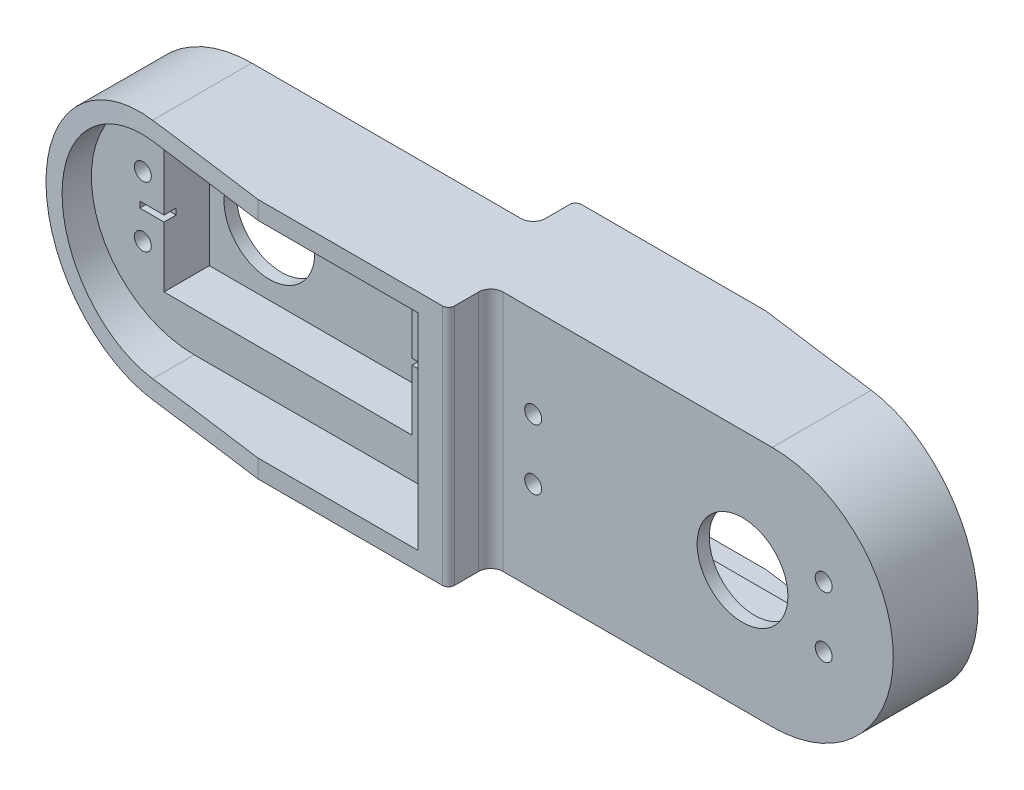
SolidWorks part; units mm, degrees
ref_plane "Front Plane" through (0, 0, 0) normal (0, 0, 1) x (1, 0, 0)
ref_plane "Top Plane" through (0, 0, 0) normal (0, 1, 0) x (1, 0, 0)
ref_plane "Right Plane" through (0, 0, 0) normal (1, 0, 0) x (0, 0, -1)
sketch "Sketch1" plane through (0, 0, 0) normal (0, 0, 1) x (1, 0, 0)
  line L0 (0, -20) -> (0, 20) construction
  line L1 (-69, -20) -> (69, -20)
  line L2 (-69, -20) -> (-69, 20)
  line L3 (-69, 20) -> (69, 20)
  line L4 (69, -20) -> (69, 20)
  line L5 (-69, -20) -> (69, 20) construction
  line L6 (-69, 20) -> (69, -20) construction
  line L7 (54, 10.5) -> (13, -10.5) construction
  line L8 (-54, -10.5) -> (-13, -10.5)
  line L9 (-54, -10.5) -> (-54, 10.5)
  line L10 (-54, 10.5) -> (-13, 10.5)
  line L11 (-13, -10.5) -> (-13, 10.5)
  line L12 (-54, -10.5) -> (-13, 10.5) construction
  line L13 (-54, 10.5) -> (-13, -10.5) construction
  line L14 (54, -10.5) -> (13, 10.5) construction
  line L15 (13, -10.5) -> (13, 10.5)
  line L16 (54, 10.5) -> (13, 10.5)
  line L17 (54, -10.5) -> (54, 10.5)
  line L18 (54, -10.5) -> (13, -10.5)
  point P0 (0, 0)
  point P6 (-33.5, 0)
  point P9 (0, 0)
  point P19 (33.5, 0)
  dimension "D1" = 138
  dimension "D2" = 40
  dimension "D3" = 15
  dimension "D4" = 41
  dimension "D5" = 21
extrude "Boss-Extrude1" add sketch "Sketch1" along normal blind 12
fillet "Fillet1" 2 edges at (-69, 20, 6) (-69, -20, 6) type full round first side face at (0, 20, 6) second side face at (0, -20, 6) middle face at (-69, 0, 6)
fillet "Fillet2" 2 edges at (69, 20, 6) (69, -20, 6) type full round first side face at (10, 20, 6) second side face at (10, -20, 6) middle face at (69, 0, 6)
sketch "Sketch3" plane through (0, 0, 12) normal (0, 0, 1) x (1, 0, 0)
  line L0 (49, 20) -> (-49, 20) construction
  line L1 (-2.5, -20) -> (2.5, -20)
  line L2 (-2.5, -17) -> (-2.5, 17)
  line L3 (-2.5, 20) -> (2.5, 20)
  line L4 (2.5, -20) -> (2.5, 20)
  line L5 (0, 0) -> (2.5, 20) construction
  line L6 (0, 0) -> (2.5, -20) construction
  line L7 (-49, 17) -> (-2.5, 17)
  line L8 (-49, -17) -> (-2.5, -17)
  line L9 (-2.5, 20) -> (-49, 20)
  line L10 (-49, -20) -> (2.5, -20)
  arc A1 (-49, 20) -> (-49, -20) centre (-49, 0) ccw
  arc A2 (-49, 17) -> (-49, -17) centre (-49, 0) ccw
  arc A3 (-49, 17) -> (-49, -17) centre (-49, 0) ccw
  point P0 (0, 0)
  line M9 (-49, -20) -> (49, -20)
  line M11 (49, 20) -> (-49, 20)
  arc M12 (-49, 20) -> (-49, -20) centre (-49, 0) ccw
  dimension "D2" = 5
  dimension "D1" = 3
extrude "Boss-Extrude3" add sketch "Sketch3" along normal blind 7 contours L4 A3 L7 L2 L8 M9 M11 M12 region at (-25.75, -19.1807, 12)
sketch "Sketch5" plane through (0, 0, 0) normal (0, 0, -1) x (-1, 0, 0)
  line L0 (-2.5, -20) -> (2.5, -20)
  line L1 (-2.5, -17) -> (-2.5, 17)
  line L2 (-2.5, 20) -> (2.5, 20)
  line L3 (2.5, -20) -> (2.5, 20)
  line L4 (0, 0) -> (2.5, 20) construction
  line L5 (0, 0) -> (2.5, -20) construction
  line L6 (-49, 17) -> (-2.5, 17)
  line L7 (-49, -17) -> (-2.5, -17)
  line L8 (-2.5, 20) -> (-49, 20)
  line L9 (-49, -20) -> (2.5, -20)
  line L10 (-69, 0) -> (-40.6504, 0) construction
  line L11 (-49, 20) -> (-49, -20) construction
  line L12 (13, -10.5) -> (13, 10.5) construction
  line L13 (49, -20) -> (-49, -20) construction
  arc A0 (-49, 20) -> (-49, -20) centre (-49, 0) ccw
  arc A1 (-49, 17) -> (-49, -17) centre (-49, 0) ccw
  arc A2 (-49, 20) -> (-49, -20) centre (-49, 0) ccw construction
  point P0 (37.3856, -38.3424)
  line M4 (49, 20) -> (-49, 20)
  arc M5 (-49, 20) -> (-49, -20) centre (-49, 0) ccw
  line M6 (-49, -20) -> (49, -20)
  dimension "D2" = 10.5
  dimension "D5" = 17
  dimension "D6" = 24.3856
  dimension "D7" = 18.3424
  dimension "D1" = 5
extrude "Boss-Extrude4" add sketch "Sketch5" along normal blind 7 contours L3 A1 L6 L1 L7 M6 M4 M5 region at (25.75, -19.1807, 0)
sketch "Sketch6" plane through (0, 0, 0) normal (0, 1, 0) x (1, 0, 0)
  line L0 (-69, -19) -> (-29, -19)
  line L1 (-69, -19) -> (-69, -14)
  line L2 (-69, 0) -> (-69, -19) construction
  line L3 (69, 7) -> (29, 7)
  line L4 (-2.5, 7) -> (49, 7) construction
  line L5 (69, 7) -> (69, 2)
  line L6 (69, -12) -> (69, 7) construction
  spline S0 degree 2 poles (-69, -14) (-48.9668, -16.2376) (-29, -19) knots 0 0 0 1 1 1
  spline S1 degree 2 poles (69, 2) (48.9668, 4.2376) (29, 7) knots 0 0 0 1 1 1
  dimension "D1" = 40
  dimension "D2" = 5
  dimension "D3" = 40
  dimension "D4" = 5
  dimension "D5" = 25
  dimension "D6" = 25
  dimension "D7" = 2
  dimension "D8" = 2
extrude "Cut-Extrude1" cut sketch "Sketch6" against normal through all both and the other way through all
sketch "Sketch8" plane through (0, 0, 12) normal (0, 0, 1) x (1, 0, 0)
  line L0 (-49, -17) -> (-2.5, -17) construction
  line L1 (-2.5, -17) -> (-2.5, 17) construction
  line L2 (-29, 17) -> (-2.5, 17) construction
  line L3 (-49, 17) -> (-29, 17) construction
  line L4 (-49, -17) -> (-2.5, -17)
  line L5 (-2.5, -17) -> (-2.5, 17)
  line L6 (-29, 17) -> (-2.5, 17)
  line L7 (-49, 17) -> (-29, 17)
  arc A0 (-49, 17) -> (-49, -17) centre (-49, 0) ccw construction
  arc A1 (-49, 17) -> (-49, -17) centre (-49, 0) ccw
extrude "Cut-Extrude2" cut sketch "Sketch8" against normal blind 2.5
sketch "Sketch9" plane through (0, 0, 0) normal (0, 0, -1) x (-1, 0, 0)
  line L0 (-49, -17) -> (-2.5, -17) construction
  line L1 (-2.5, -17) -> (-2.5, 17) construction
  line L2 (-49, 17) -> (-2.5, 17) construction
  line L3 (-49, 17) -> (-29, 17) construction
  line L4 (-49, -17) -> (-2.5, -17)
  line L5 (-2.5, -17) -> (-2.5, 17)
  line L6 (-49, 17) -> (-2.5, 17)
  line L7 (-49, 17) -> (-29, 17)
  arc A0 (-49, 17) -> (-49, -17) centre (-49, 0) ccw construction
  arc A1 (-49, 17) -> (-49, -17) centre (-49, 0) ccw
  line M1 (-13, -10.5) -> (-54, -10.5)
  line M2 (-54, -10.5) -> (-54, 10.5)
  line M3 (-54, 10.5) -> (-13, 10.5)
  line M4 (-13, 10.5) -> (-13, -10.5)
  line M5 (-2.5, 17) -> (-49, 17)
  arc M6 (-49, 17) -> (-49, -17) centre (-49, 0) ccw
  line M7 (-49, -17) -> (-2.5, -17)
  line M8 (-2.5, -17) -> (-2.5, 17)
extrude "Cut-Extrude3" cut sketch "Sketch9" against normal blind 2.5 contours L6 M8 M5 M6 M7 M4 M1 M2 M3 region at (65.2797, 0, 0)
sketch "Sketch10" plane through (0, 0, 12) normal (0, 0, 1) x (1, 0, 0)
  line L0 (54, -10.5) -> (54, 10.5) construction
  line L1 (13, -10.5) -> (54, -10.5) construction
  line L2 (13, 10.5) -> (13, -10.5) construction
  line L3 (54, 10.5) -> (13, 10.5) construction
  line L4 (54, -10.5) -> (54, 10.5)
  line L5 (13, -10.5) -> (54, -10.5)
  line L6 (13, 10.5) -> (13, -10.5)
  line L7 (54, 10.5) -> (13, 10.5)
  circle A0 centre (44.09, 0) radius 7.5
  point P7 (54, 0)
  dimension "D1" = 15
  dimension "D2" = 9.91
extrude "Boss-Extrude5" add sketch "Sketch10" against normal blind 2
sketch "Sketch11" plane through (0, 0, 0) normal (0, 0, -1) x (-1, 0, 0)
  line L0 (54, -10.5) -> (13, -10.5) construction
  line L1 (13, -10.5) -> (13, 10.5) construction
  line L2 (13, 10.5) -> (54, 10.5) construction
  line L3 (54, 10.5) -> (54, -10.5) construction
  line L4 (54, -10.5) -> (13, -10.5)
  line L5 (13, -10.5) -> (13, 10.5)
  line L6 (13, 10.5) -> (54, 10.5)
  line L7 (54, 10.5) -> (54, -10.5)
  circle A0 centre (44.09, 0) radius 7.5
  dimension "D1" = 15
  dimension "D2" = 9.91
extrude "Boss-Extrude6" add sketch "Sketch11" against normal blind 2
sketch "Sketch12" plane through (0, 0, 9.5) normal (0, 0, 1) x (1, 0, 0)
  line L0 (-66, 0) -> (-2.5, 0) construction
  line L1 (-2.5, -17) -> (-2.5, 17) construction
  line L2 (-54, 0.5) -> (-58, 0.5)
  line L3 (-54, -10.5) -> (-54, 10.5) construction
  line L4 (-58, 0.5) -> (-58, -0.5)
  line L5 (-58, -0.5) -> (-54, -0.5)
  line L6 (-33.5, 10.5) -> (-33.5, -10.5) construction
  line L7 (-54, 10.5) -> (-13, 10.5) construction
  line L8 (-13, -10.5) -> (-54, -10.5) construction
  line L9 (-9, -0.5) -> (-13, -0.5)
  line L10 (-9, 0.5) -> (-9, -0.5)
  line L11 (-13, 0.5) -> (-9, 0.5)
  line L12 (-54, 0.5) -> (-54, -0.5)
  line L13 (-13, 0.5) -> (-13, -0.5)
  arc A0 (-49, 17) -> (-49, -17) centre (-49, 0) ccw construction
  dimension "D1" = 0.5
  dimension "D2" = 0.5
  dimension "D3" = 4
extrude "Cut-Extrude4" cut sketch "Sketch12" against normal blind 2
sketch "Sketch13" plane through (0, 0, 2.5) normal (0, 0, -1) x (-1, 0, 0)
  line L0 (-33.5, 10.5) -> (-33.5, -10.5) construction
  line L4 (-54, 10.5) -> (-13, 10.5) construction
  line L10 (-13, -10.5) -> (-54, -10.5) construction
  line L12 (-2.5, -17) -> (-2.5, 17) construction
  line L13 (-49, -17) -> (-2.5, -17) construction
  line L14 (-66, 0) -> (-2.5, 0) construction
  line L15 (-2.5, -17) -> (-2.5, 17) construction
  line L16 (-54, 0.5) -> (-57, 0.5)
  line L17 (-54, -10.5) -> (-54, 10.5) construction
  line L18 (-57, 0.5) -> (-57, -0.5)
  line L19 (-57, -0.5) -> (-54, -0.5)
  line L20 (-54, -10.5) -> (-54, 10.5) construction
  line L21 (-54, -0.5) -> (-54, 0.5)
  line L22 (-13, -0.5) -> (-13, 0.5)
  line L23 (-10, -0.5) -> (-13, -0.5)
  line L24 (-10, 0.5) -> (-10, -0.5)
  line L25 (-13, 0.5) -> (-10, 0.5)
  arc A0 (-49, 17) -> (-49, -17) centre (-49, 0) ccw construction
  dimension "D1" = 3
  dimension "D2" = 0.5
  dimension "D3" = 0.5
extrude "Cut-Extrude5" cut sketch "Sketch13" against normal blind 2
fillet "Fillet4" radius 2 1 edges at (2.5, 0, 12)
fillet "Fillet5" radius 2 1 edges at (-2.5, 0, 0)
fillet "Fillet6" radius 1 2 edges at (2.5, 0, 19) (-2.5, 0, -7)
sketch "Sketch14" plane through (0, 0, 2.5) normal (0, 0, -1) x (-1, 0, 0)
  line L0 (-66, 0) -> (-2.5, 0) construction
  line L1 (-2.5, -17) -> (-2.5, 17) construction
  line L2 (-33.5, 10.5) -> (-33.5, -10.5) construction
  line L3 (-54, 10.5) -> (-13, 10.5) construction
  line L4 (-13, -10.5) -> (-54, -10.5) construction
  line L6 (-57.5, -5) -> (-9.5, -5) construction
  line L7 (-57.5, -5) -> (-57.5, 5) construction
  line L8 (-57.5, 5) -> (-9.5, 5) construction
  line L9 (-9.5, -5) -> (-9.5, 5) construction
  line L10 (-57.5, -5) -> (-9.5, 5) construction
  line L11 (-57.5, 5) -> (-9.5, -5) construction
  arc A0 (-49, 17) -> (-49, -17) centre (-49, 0) ccw construction
  circle A1 centre (-57.5, 5) radius 1.4
  circle A2 centre (-57.5, -5) radius 1.4
  circle A3 centre (-9.5, 5) radius 1.4
  circle A4 centre (-9.5, -5) radius 1.4
  point P13 (-33.5, 0)
  dimension "D3" = 2.8
  dimension "D1" = 48
  dimension "D2" = 10
extrude "Cut-Extrude6" cut sketch "Sketch14" against normal through all
sketch "Sketch15" plane through (0, 0, 9.5) normal (0, 0, 1) x (1, 0, 0)
  line L0 (-33.5, 10.5) -> (-33.5, -10.5) construction
  line L1 (-54, 10.5) -> (-13, 10.5) construction
  line L2 (-13, -10.5) -> (-54, -10.5) construction
  line L3 (-66, 0) -> (-2.5, 0) construction
  line L4 (-2.5, -17) -> (-2.5, 17) construction
  line L6 (-57.5, -5) -> (-9.5, -5) construction
  line L7 (-57.5, -5) -> (-57.5, 5) construction
  line L8 (-57.5, 5) -> (-9.5, 5) construction
  line L9 (-9.5, -5) -> (-9.5, 5) construction
  line L10 (-57.5, -5) -> (-9.5, 5) construction
  line L11 (-57.5, 5) -> (-9.5, -5) construction
  arc A0 (-49, 17) -> (-49, -17) centre (-49, 0) ccw construction
  circle A1 centre (-57.5, 5) radius 1.4
  circle A2 centre (-57.5, -5) radius 1.4
  circle A3 centre (-9.5, -5) radius 1.4
  circle A4 centre (-9.5, 5) radius 1.4
  point P13 (-33.5, 0)
  dimension "D3" = 2.8
  dimension "D1" = 10
  dimension "D2" = 48
extrude "Cut-Extrude7" cut sketch "Sketch15" against normal through all
